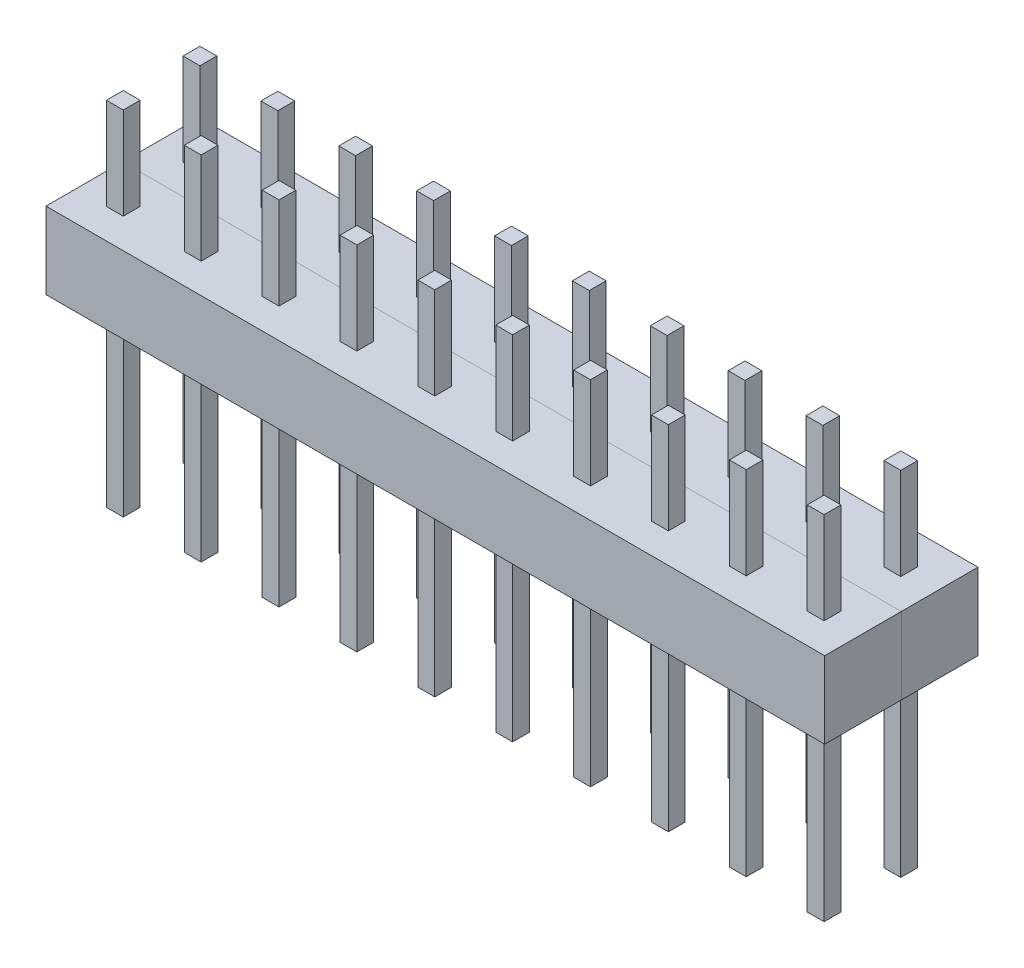
SolidWorks part; units mm, degrees
ref_plane "Front Plane" through (0, 0, 0) normal (0, 0, 1) x (1, 0, 0)
ref_plane "Top Plane" through (0, 0, 0) normal (0, 1, 0) x (1, 0, 0)
ref_plane "Right Plane" through (0, 0, 0) normal (1, 0, 0) x (0, 0, -1)
sketch "Sketch1" plane through (0, 0, 0) normal (0, 0, 1) x (1, 0, 0)
  line L1 (0, 0) -> (25.4, 0)
  line L2 (0, 0) -> (0, 2.5)
  line L3 (0, 2.5) -> (25.4, 2.5)
  line L4 (25.4, 0) -> (25.4, 2.5)
  dimension "D1" = 2.5
  dimension "D2" = 25.4
extrude "Boss-Extrude1" add sketch "Sketch1" along normal mid plane 2.5
sketch "Sketch2" plane through (0, 0, 0) normal (0, -1, 0) x (1, 0, 0)
  line L0 (0, 0) -> (25.4, 0) construction
  line L1 (25.4, 1.25) -> (25.4, -1.25) construction
  line L2 (3.535, -0.275) -> (4.085, -0.275)
  line L3 (0.995, -0.275) -> (1.545, -0.275)
  line L4 (0.995, -0.275) -> (0.995, 0.275)
  line L5 (0.995, 0.275) -> (1.545, 0.275)
  line L6 (1.545, -0.275) -> (1.545, 0.275)
  line L7 (0.995, -0.275) -> (1.545, 0.275) construction
  line L8 (0.995, 0.275) -> (1.545, -0.275) construction
  line L9 (3.535, -0.275) -> (3.535, 0.275)
  line L10 (3.535, 0.275) -> (4.085, 0.275)
  line L11 (4.085, -0.275) -> (4.085, 0.275)
  line L12 (3.535, -0.275) -> (4.085, 0.275) construction
  line L13 (3.535, 0.275) -> (4.085, -0.275) construction
  line L14 (1.27, 0) -> (3.81, 0) construction
  line L15 (6.075, -0.275) -> (6.625, -0.275)
  line L16 (6.075, -0.275) -> (6.075, 0.275)
  line L17 (6.075, 0.275) -> (6.625, 0.275)
  line L18 (6.625, -0.275) -> (6.625, 0.275)
  line L19 (6.075, -0.275) -> (6.625, 0.275) construction
  line L20 (6.075, 0.275) -> (6.625, -0.275) construction
  line L21 (8.615, -0.275) -> (9.165, -0.275)
  line L22 (8.615, -0.275) -> (8.615, 0.275)
  line L23 (8.615, 0.275) -> (9.165, 0.275)
  line L24 (9.165, -0.275) -> (9.165, 0.275)
  line L25 (8.615, -0.275) -> (9.165, 0.275) construction
  line L26 (8.615, 0.275) -> (9.165, -0.275) construction
  line L27 (11.155, -0.275) -> (11.705, -0.275)
  line L28 (11.155, -0.275) -> (11.155, 0.275)
  line L29 (11.155, 0.275) -> (11.705, 0.275)
  line L30 (11.705, -0.275) -> (11.705, 0.275)
  line L31 (11.155, -0.275) -> (11.705, 0.275) construction
  line L32 (11.155, 0.275) -> (11.705, -0.275) construction
  line L33 (13.695, -0.275) -> (14.245, -0.275)
  line L34 (13.695, -0.275) -> (13.695, 0.275)
  line L35 (13.695, 0.275) -> (14.245, 0.275)
  line L36 (14.245, -0.275) -> (14.245, 0.275)
  line L37 (13.695, -0.275) -> (14.245, 0.275) construction
  line L38 (13.695, 0.275) -> (14.245, -0.275) construction
  line L39 (16.235, -0.275) -> (16.785, -0.275)
  line L40 (16.235, -0.275) -> (16.235, 0.275)
  line L41 (16.235, 0.275) -> (16.785, 0.275)
  line L42 (16.785, -0.275) -> (16.785, 0.275)
  line L43 (16.235, -0.275) -> (16.785, 0.275) construction
  line L44 (16.235, 0.275) -> (16.785, -0.275) construction
  line L45 (18.775, -0.275) -> (19.325, -0.275)
  line L46 (18.775, -0.275) -> (18.775, 0.275)
  line L47 (18.775, 0.275) -> (19.325, 0.275)
  line L48 (19.325, -0.275) -> (19.325, 0.275)
  line L49 (18.775, -0.275) -> (19.325, 0.275) construction
  line L50 (18.775, 0.275) -> (19.325, -0.275) construction
  line L51 (21.315, -0.275) -> (21.865, -0.275)
  line L52 (21.315, -0.275) -> (21.315, 0.275)
  line L53 (21.315, 0.275) -> (21.865, 0.275)
  line L54 (21.865, -0.275) -> (21.865, 0.275)
  line L55 (21.315, -0.275) -> (21.865, 0.275) construction
  line L56 (21.315, 0.275) -> (21.865, -0.275) construction
  line L57 (23.855, -0.275) -> (24.405, -0.275)
  line L58 (23.855, -0.275) -> (23.855, 0.275)
  line L59 (23.855, 0.275) -> (24.405, 0.275)
  line L60 (24.405, -0.275) -> (24.405, 0.275)
  line L61 (23.855, -0.275) -> (24.405, 0.275) construction
  line L62 (23.855, 0.275) -> (24.405, -0.275) construction
  point P5 (1.27, 0)
  point P12 (3.81, 0)
  point P18 (6.35, 0)
  point P23 (8.89, 0)
  point P28 (11.43, 0)
  point P33 (13.97, 0)
  point P38 (16.51, 0)
  point P43 (19.05, 0)
  point P48 (21.59, 0)
  point P53 (24.13, 0)
  dimension "D1" = 0.55
  dimension "D3" = 1.27
  dimension "D4" = 2.54
  dimension "D2" = 10
extrude "Boss-Extrude2" add sketch "Sketch2" along normal blind 6 separate body
ref_axis "Axis1" through (1.27, 0, 0) along (0, -1, 0)
ref_axis "Axis2" through (24.13, 0, 0) along (0, -1, 0)
extrude "Boss-Extrude3" add sketch "Sketch2<2>" against normal blind 5.5 separate body
sketch "Sketch2<2>" plane through (0, 0, 0) normal (0, -1, 0) x (1, 0, 0) same geometry as "Sketch2"
mirror "Mirror1" about plane through (0, 0, 1.25) normal (0, 0, -1) of bodies 101 105 106 121 122 123 124 125 126 127 128 114 113 112 111 110 109 108 107 104 103
